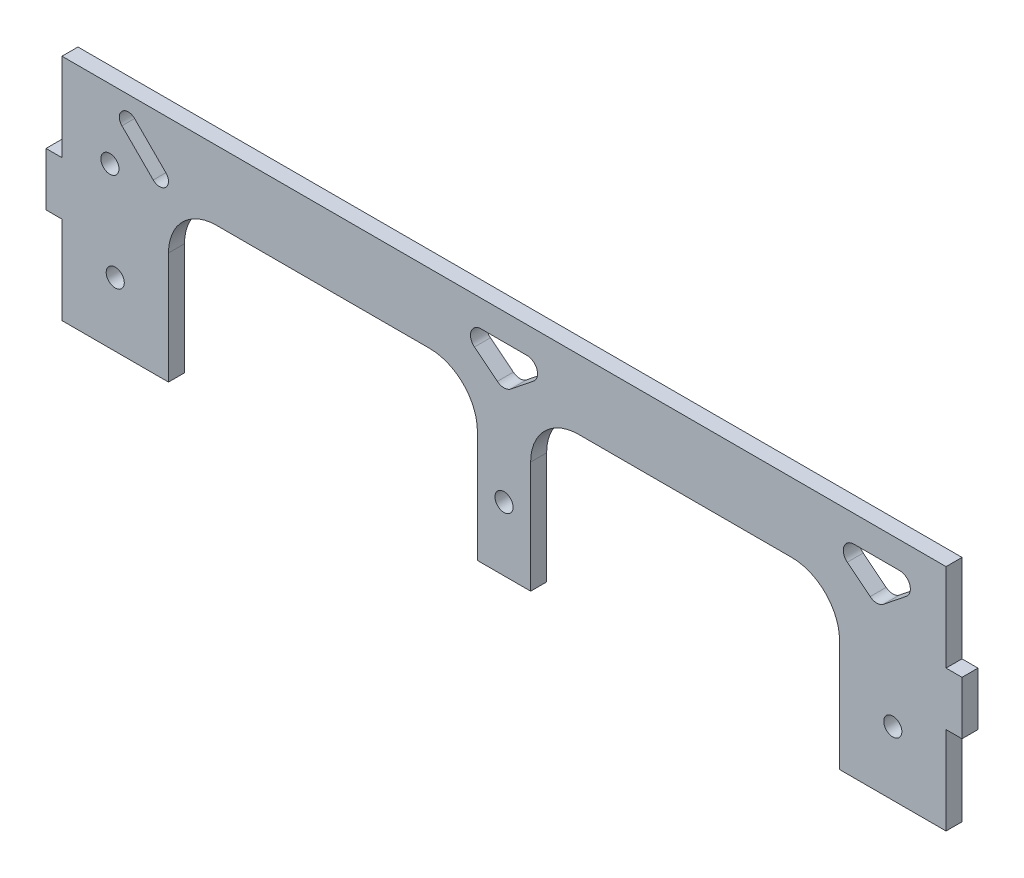
SolidWorks part; units mm, degrees
ref_plane "Front Plane" through (0, 0, 0) normal (0, 0, 1) x (1, 0, 0)
ref_plane "Top Plane" through (0, 0, 0) normal (0, 1, 0) x (1, 0, 0)
ref_plane "Right Plane" through (0, 0, 0) normal (1, 0, 0) x (0, 0, -1)
sketch "Sketch1" plane through (0, 0, 0) normal (0, 0, 1) x (1, 0, 0)
  line L0 (0, 0) -> (0, 16.5)
  line L1 (0, 43) -> (166, 43)
  line L2 (166, 43) -> (166, 26.5)
  line L3 (166, 0) -> (146, 0)
  line L4 (146, 0) -> (146, 30)
  line L5 (146, 30) -> (88, 30)
  line L6 (88, 30) -> (88, 0)
  line L7 (88, 0) -> (78, 0)
  line L8 (78, 0) -> (78, 30)
  line L9 (78, 30) -> (20, 30)
  line L10 (20, 30) -> (20, 0)
  line L11 (20, 0) -> (0, 0)
  line L12 (0, 26.5) -> (-3, 26.5)
  line L13 (-3, 26.5) -> (-3, 16.5)
  line L14 (-3, 16.5) -> (0, 16.5)
  line L15 (0, 26.5) -> (0, 43)
  line L16 (83, 43) -> (83, 0) construction
  line L17 (83, 21.5) -> (0, 21.5) construction
  line L18 (-3, 21.5) -> (20, 21.5) construction
  line L19 (169, 16.5) -> (166, 16.5)
  line L20 (169, 26.5) -> (169, 16.5)
  line L21 (166, 26.5) -> (169, 26.5)
  line L22 (166, 16.5) -> (166, 0)
  dimension "D1" = 30
  dimension "D2" = 10
  dimension "D3" = 58
  dimension "D4" = 20
  dimension "D5" = 13
  dimension "D6" = 20
  dimension "D7" = 10
  dimension "D8" = 3
extrude "Boss-Extrude1" add sketch "Sketch1" along normal blind 3
fillet "Fillet1" radius 9 4 edges at (146, 30, 1.5) (88, 30, 1.5) (78, 30, 1.5) (20, 30, 1.5)
fillet "Fillet2" [suppressed] radius 9
sketch "Sketch2" plane through (0, 0, 3) normal (0, 0, 1) x (1, 0, 0)
  line L0 (83, 43) -> (83, 0) construction
  line L1 (166, 43) -> (0, 43) construction
  line L2 (78, 0) -> (88, 0) construction
  line L3 (10, 0) -> (10, 43) construction
  line L4 (0, 0) -> (20, 0) construction
  line L5 (156, 0) -> (156, 43) construction
  line L6 (146, 0) -> (166, 0) construction
  line L7 (10, 12) -> (162.8081, 12) construction
  circle A0 centre (10, 12) radius 1.7
  circle A1 centre (83, 12) radius 1.7
  circle A2 centre (156, 12) radius 1.7
  circle A3 centre (10, 12) radius 1.7 construction
  point P20 (0, 0)
  dimension "D1" = 3.4
  dimension "D5" = 3.4
  dimension "D6" = 3.4
extrude "Cut-Extrude1" cut sketch "Sketch2" against normal through all
sketch "Sketch3" plane through (0, 0, 3) normal (0, 0, 1) x (1, 0, 0)
  circle A0 centre (9, 30) radius 1.7
  dimension "D1" = 3.4
extrude "Cut-Extrude2" cut sketch "Sketch3" against normal through all
sketch "Sketch4" plane through (0, 0, 3) normal (0, 0, 1) x (1, 0, 0)
  line L0 (73, 38) -> (83, 30)
  line L1 (83, 30) -> (93, 38)
  line L2 (93, 38) -> (73, 38)
  line L3 (166, 43) -> (0, 43) construction
  line L4 (83, 0) -> (83, 43) construction
  line L5 (78, 0) -> (88, 0) construction
  line L6 (143, 38) -> (153, 30)
  line L7 (153, 30) -> (163, 38)
  line L8 (163, 38) -> (143, 38)
  dimension "D1" = 20
  dimension "D2" = 5
  dimension "D3" = 8
  dimension "D4" = 2
extrude "Cut-Extrude3" cut sketch "Sketch4" against normal through all
fillet "Fillet3" radius 2 6 edges at (83, 30, 1.5) (93, 38, 1.5) (73, 38, 1.5) (153, 30, 1.5) (163, 38, 1.5) (143, 38, 1.5)
sketch "Sketch5" plane through (0, 0, 3) normal (0, 0, 1) x (1, 0, 0)
  line L0 (12.4474, 38.4962) -> (18.3228, 32.6207) construction
  line L1 (13.6312, 39.6801) -> (19.5067, 33.8046)
  line L2 (11.2635, 37.3123) -> (17.139, 31.4369)
  arc A0 (13.6312, 39.6801) -> (11.2635, 37.3123) centre (12.4474, 38.4962) ccw
  arc A1 (17.139, 31.4369) -> (19.5067, 33.8046) centre (18.3228, 32.6207) ccw
  point P2 (15.3851, 35.5585)
extrude "Cut-Extrude4" cut sketch "Sketch5" against normal through all
